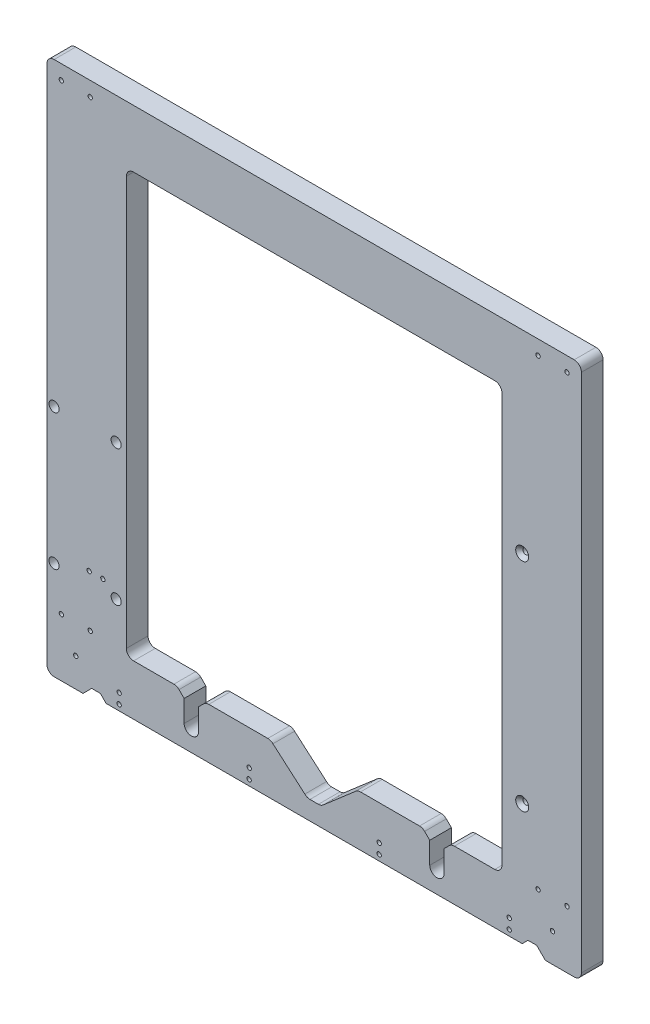
SolidWorks part; units mm, degrees
ref_plane "Plano frontal" through (0, 0, 0) normal (0, 0, 1) x (1, 0, 0)
ref_plane "Plano superior" through (0, 0, 0) normal (0, 1, 0) x (1, 0, 0)
ref_plane "Plano direito" through (0, 0, 0) normal (1, 0, 0) x (0, 0, -1)
sketch "Model" plane through (0, 0, 0) normal (0, 0, 1) x (1, 0, 0)
  line L0 (45.9594, 55.5362) -> (45.9594, 415.5362)
  line L1 (50.9594, 420.5362) -> (410.9594, 420.5362)
  line L2 (415.9594, 415.5362) -> (415.9594, 55.5362)
  line L3 (410.9594, 50.5362) -> (390.9594, 50.5362)
  line L4 (390.9594, 50.5362) -> (388.9594, 52.5362)
  line L5 (374.9594, 52.5362) -> (86.9594, 52.5362)
  line L6 (72.9594, 52.5362) -> (70.9594, 50.5362)
  line L7 (70.9594, 50.5362) -> (50.9594, 50.5362)
  line L8 (140.9594, 67.5362) -> (140.9594, 82.5362)
  line L9 (140.9594, 82.5362) -> (137.4239, 86.0718)
  line L10 (198.8884, 87.5362) -> (158.0305, 87.5362)
  line L11 (133.8884, 87.5362) -> (105.9594, 87.5362)
  line L12 (100.9594, 92.5362) -> (100.9594, 375.5362)
  line L13 (105.9594, 380.5362) -> (355.9594, 380.5362)
  line L14 (360.9594, 375.5362) -> (360.9594, 92.5362)
  line L15 (150.9594, 67.5362) -> (150.9594, 82.5362)
  line L16 (150.9594, 82.5362) -> (154.495, 86.0718)
  line L17 (320.9594, 82.5362) -> (320.9594, 67.5362)
  line L18 (310.9594, 67.5362) -> (310.9594, 82.5362)
  line L19 (310.9594, 82.5362) -> (307.4239, 86.0718)
  line L20 (228.0305, 65.5362) -> (233.8884, 65.5362)
  line L21 (237.4239, 67.0007) -> (259.495, 86.0718)
  line L22 (224.495, 67.0007) -> (202.4239, 86.0718)
  line L23 (263.0305, 87.5362) -> (303.8884, 87.5362)
  line L24 (388.9594, 52.5362) -> (384.9594, 56.5362)
  line L25 (384.9594, 56.5362) -> (378.9594, 56.5362)
  line L26 (378.9594, 56.5362) -> (374.9594, 52.5362)
  line L27 (72.9594, 52.5362) -> (76.9594, 56.5362)
  line L28 (76.9594, 56.5362) -> (82.9594, 56.5362)
  line L29 (82.9594, 56.5362) -> (86.9594, 52.5362)
  line L30 (328.0305, 87.5362) -> (355.9594, 87.5362)
  line L31 (320.9594, 82.5362) -> (324.495, 86.0718)
  arc A0 (140.9594, 67.5362) -> (150.9594, 67.5362) centre (145.9594, 67.5362) ccw
  arc A1 (310.9594, 67.5362) -> (320.9594, 67.5362) centre (315.9594, 67.5362) ccw
  circle A2 centre (95.9594, 56.5362) radius 1.5
  circle A3 centre (365.9594, 56.5362) radius 1.5
  circle A4 centre (275.9594, 56.5362) radius 1.5
  circle A5 centre (185.9594, 56.5362) radius 1.5
  circle A6 centre (55.9594, 90.5362) radius 1.5
  circle A7 centre (75.9594, 90.5362) radius 1.5
  circle A8 centre (65.9594, 70.5362) radius 1.5
  circle A9 centre (395.9594, 70.5362) radius 1.5
  circle A10 centre (385.9594, 90.5362) radius 1.5
  circle A11 centre (405.9594, 90.5362) radius 1.5
  circle A12 centre (405.9594, 410.5362) radius 1.5
  circle A13 centre (385.9594, 410.5362) radius 1.5
  circle A14 centre (55.9594, 410.5362) radius 1.5
  circle A15 centre (75.9594, 410.5362) radius 1.5
  circle A16 centre (93.911, 118.5016) radius 1.5
  circle A17 centre (50.911, 212.5016) radius 1.5
  circle A18 centre (93.911, 212.5016) radius 1.5
  circle A19 centre (50.8762, 118.5278) radius 1.5
  circle A20 centre (95.9594, 63.5362) radius 1.5
  circle A21 centre (365.9594, 63.5362) radius 1.5
  circle A22 centre (275.9594, 63.5362) radius 1.5
  circle A23 centre (185.9594, 63.5362) radius 1.5
  circle A24 centre (390.4594, 301.5362) radius 1.5 construction
  circle A25 centre (369.4594, 301.5362) radius 1.5 construction
  circle A26 centre (84.7094, 126.0362) radius 1.5
  circle A27 centre (75.2094, 126.0362) radius 1.5
  arc A28 (415.9594, 415.5362) -> (410.9594, 420.5362) centre (410.9594, 415.5362) ccw
  arc A29 (50.9594, 420.5362) -> (45.9594, 415.5362) centre (50.9594, 415.5362) ccw
  arc A30 (410.9594, 50.5362) -> (415.9594, 55.5362) centre (410.9594, 55.5362) ccw
  arc A31 (45.9594, 55.5362) -> (50.9594, 50.5362) centre (50.9594, 55.5362) ccw
  arc A32 (105.9594, 380.5362) -> (100.9594, 375.5362) centre (105.9594, 375.5362) ccw
  arc A33 (360.9594, 375.5362) -> (355.9594, 380.5362) centre (355.9594, 375.5362) ccw
  arc A34 (355.9594, 87.5362) -> (360.9594, 92.5362) centre (355.9594, 92.5362) ccw
  arc A35 (100.9594, 92.5362) -> (105.9594, 87.5362) centre (105.9594, 92.5362) ccw
  arc A36 (202.4239, 86.0718) -> (198.8884, 87.5362) centre (198.8884, 82.5362) ccw
  arc A37 (263.0305, 87.5362) -> (259.495, 86.0718) centre (263.0305, 82.5362) ccw
  arc A38 (233.8884, 65.5362) -> (237.4239, 67.0007) centre (233.8884, 70.5362) ccw
  arc A39 (224.495, 67.0007) -> (228.0305, 65.5362) centre (228.0305, 70.5362) ccw
  arc A40 (137.4239, 86.0718) -> (133.8884, 87.5362) centre (133.8884, 82.5362) ccw
  arc A41 (158.0305, 87.5362) -> (154.495, 86.0718) centre (158.0305, 82.5362) ccw
  arc A42 (307.4239, 86.0718) -> (303.8884, 87.5362) centre (303.8884, 82.5362) ccw
  arc A43 (328.0305, 87.5362) -> (324.495, 86.0718) centre (328.0305, 82.5362) ccw
  circle A44 centre (377.4594, 301.5362) radius 1.5 construction
  circle A45 centre (374.9594, 136.4362) radius 2 construction
  circle A46 centre (374.9594, 286.4362) radius 2 construction
  circle A47 centre (374.9594, 136.4362) radius 2
  circle A48 centre (374.9594, 286.4362) radius 2
extrude "Ressalto-extrusão1" add sketch "Model" along normal blind 15
sketch "Esboço1" plane through (0, 0, 0) normal (0, 0, -1) x (-1, 0, 0)
  circle A0 centre (-385.9594, 90.5362) radius 3.5
  circle A1 centre (-405.9594, 90.5362) radius 3.5
  circle A2 centre (-395.9594, 70.5362) radius 3.5
  circle A3 centre (-75.9594, 90.5362) radius 3.5
  circle A4 centre (-55.9594, 90.5362) radius 3.5
  circle A5 centre (-65.9594, 70.5362) radius 3.5
  circle A6 centre (-405.9594, 410.5362) radius 3.5
  circle A7 centre (-385.9594, 410.5362) radius 3.5
  circle A8 centre (-75.9594, 410.5362) radius 3.5
  circle A9 centre (-55.9594, 410.5362) radius 3.5
  circle A10 centre (-84.7094, 126.0362) radius 3.5
  circle A11 centre (-75.2094, 126.0362) radius 3.5
  dimension "D1" = 7
extrude "Corte-extrusão1" cut sketch "Esboço1" against normal blind 7
sketch "Esboço2" plane through (0, 0, 15) normal (0, 0, 1) x (1, 0, 0)
  circle A0 centre (50.911, 212.5016) radius 3.5
  circle A1 centre (93.911, 212.5016) radius 3.5
  circle A2 centre (93.911, 118.5016) radius 3.5
  circle A3 centre (50.8762, 118.5278) radius 3.5
  dimension "D1" = 7
extrude "Corte-extrusão2" cut sketch "Esboço2" against normal blind 7
chamfer "Chanfro1" distance 2.5 angle 45 2 edges at (376.9594, 136.4362, 15) (376.9594, 286.4362, 15)
